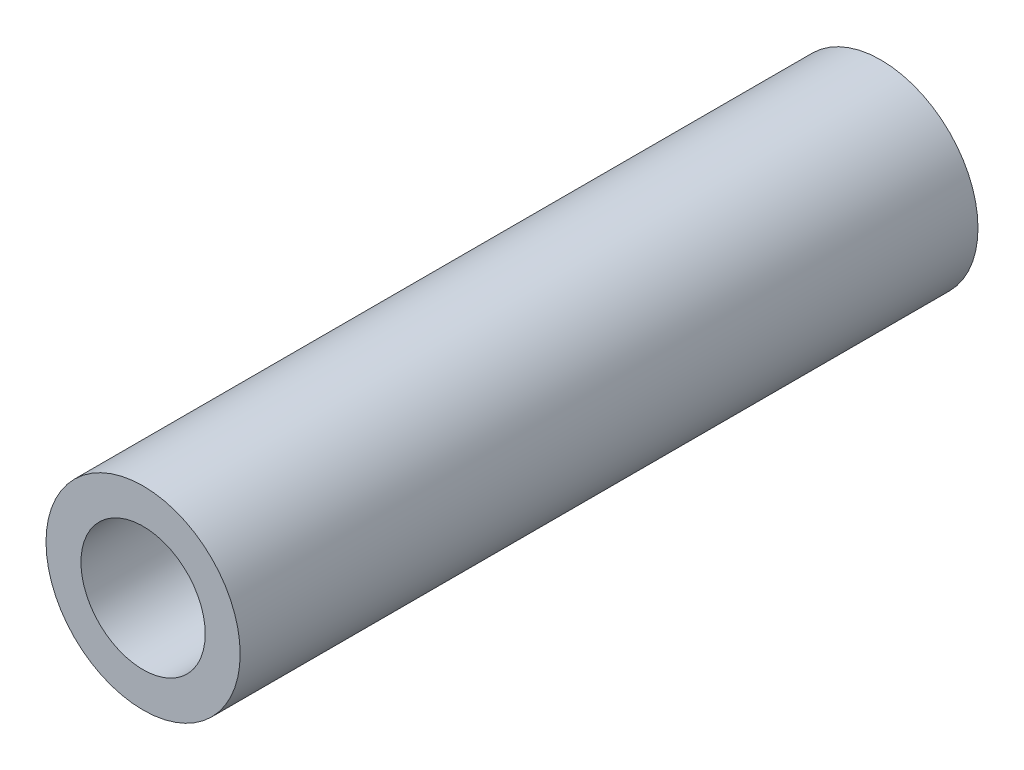
SolidWorks part; units mm, degrees
ref_plane "Front Plane" through (0, 0, 0) normal (0, 0, 1) x (1, 0, 0)
ref_plane "Top Plane" through (0, 0, 0) normal (0, 1, 0) x (1, 0, 0)
ref_plane "Right Plane" through (0, 0, 0) normal (1, 0, 0) x (0, 0, -1)
sketch "Sketch1" plane through (0, 0, 0) normal (0, 0, 1) x (1, 0, 0)
  circle A0 centre (33, 0) radius 2.5
  dimension "D1" = 5
extrude "Boss-Extrude1" add sketch "Sketch1" along normal blind 19
sketch "Sketch3" plane through (0, 0, 19) normal (0, 0, 1) x (1, 0, 0)
  circle A0 centre (33, 0) radius 1.6
  circle A1 centre (33, 0) radius 2.1
  dimension "D1" = 3.2
  dimension "D2" = 4.2
extrude "Cut-Extrude1" cut sketch "Sketch3" against normal up to next contours A0
equation "\"RingPostIn\"=5"
equation "\"D1@Sketch1\"=\"RingPostIn\""
equation "\"RingPinShaft\"= 5"
equation "\"CenterBearingOut\"=32"
equation "\"m3Thru\"=3.2"
equation "\"D1@Sketch3\"=\"m3Thru\""
equation "\"m3Insert\"=4.2"
equation "\"D2@Sketch3\"=\"m3Insert\""
